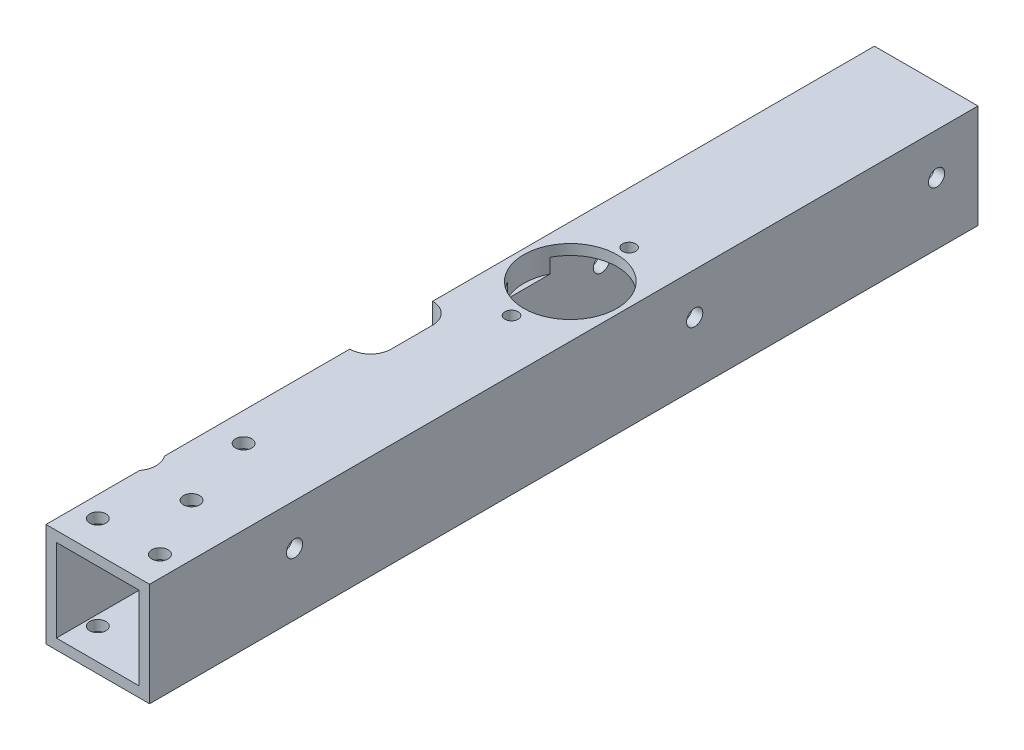
SolidWorks part; units mm, degrees
material "6061 Alloy"
ref_plane "Front Plane" through (0, 0, 0) normal (0, 0, 1) x (1, 0, 0)
ref_plane "Top Plane" through (0, 0, 0) normal (0, 1, 0) x (1, 0, 0)
ref_plane "Right Plane" through (0, 0, 0) normal (1, 0, 0) x (0, 0, -1)
sketch "Sketch1" plane through (0, 0, 0) normal (0, 0, 1) x (1, 0, 0)
  line L0 (-12.7, 12.7) -> (12.7, 12.7)
  line L2 (-15.875, 15.875) -> (15.875, 15.875)
  line L3 (-15.875, 15.875) -> (-15.875, -15.875)
  line L4 (-15.875, -15.875) -> (15.875, -15.875)
  line L5 (15.875, 15.875) -> (15.875, -15.875)
  line L10 (12.7, 12.7) -> (12.7, -12.7)
  line L11 (-12.7, -12.7) -> (12.7, -12.7)
  line L12 (-12.7, 12.7) -> (-12.7, -12.7)
  point P12 (0, 15.875)
  point P14 (15.875, 0)
  dimension "Wall Thickness" = 3.175
  dimension "Outside Width" = 31.75
  dimension "Outside Height" = 31.75
  dimension "Inside Height" = 25.4
  dimension "Inside Width" = 25.4
sketch "Sketch2" plane through (0, 0, 0) normal (1, 0, 0) x (0, 0, -1)
  line L0 (127, 0) -> (-127, 0)
  point P4 (0, 0)
  point P7 (-127, 0)
  point P10 (127, 0)
  dimension "Length" = 254
sketch "Sketch3" plane through (0, 0, 0) normal (0, 0, 1) x (1, 0, 0)
  line L21 (15.875, 15.875) -> (-15.875, 15.875)
  line L22 (15.875, -15.875) -> (15.875, 15.875)
  line L23 (-15.875, -15.875) -> (15.875, -15.875)
  line L24 (-15.875, 15.875) -> (-15.875, -15.875)
  line L25 (15.875, 15.875) -> (-15.875, 15.875)
  line L26 (15.875, -15.875) -> (15.875, 15.875)
  line L27 (-15.875, -15.875) -> (15.875, -15.875)
  line L28 (-15.875, 15.875) -> (-15.875, -15.875)
  line L29 (12.7, 12.7) -> (-12.7, 12.7)
  line L30 (12.7, -12.7) -> (12.7, 12.7)
  line L31 (-12.7, -12.7) -> (12.7, -12.7)
  line L32 (-12.7, 12.7) -> (-12.7, -12.7)
  line L33 (12.7, 12.7) -> (-12.7, 12.7)
  line L34 (12.7, -12.7) -> (12.7, 12.7)
  line L35 (-12.7, -12.7) -> (12.7, -12.7)
  line L36 (-12.7, 12.7) -> (-12.7, -12.7)
  dimension "D1" = 0
  dimension "D2" = 0
extrude "Boss-Extrude1" add sketch "Sketch3" along normal up to vertex (127 mm away) and the other way up to vertex (127 mm away) up to point (0, 0, 127) other way up to point (0, 0, -127)
sketch "Drawing Reference" plane through (0, 0, 0) normal (1, 0, 0) x (0, 0, -1)
  line L0 (-127, 0) -> (127, 0) construction
  line L1 (0, -15.875) -> (0, 15.875) construction
  line L2 (-127, -15.875) -> (127, -15.875) construction
  line L5 (-127, 15.875) -> (127, 15.875) construction
  point P7 (-104.14, 0)
  point P8 (104.14, 0)
  dimension "D1" = 22.86
sketch "Sketch4" plane through (0, 15.875, 0) normal (0, 1, 0) x (1, 0, 0)
  line L0 (0, -127) -> (0, -117.475) construction
  line L1 (15.875, -127) -> (-15.875, -127) construction
  line L2 (0, -117.475) -> (9.525, -117.475) construction
  line L3 (0, -117.475) -> (-9.525, -117.475) construction
  line L4 (0, -117.475) -> (0, 17.8816) construction
  line L5 (0, -117.475) -> (0, -98.2472) construction
  point P5 (-7.1119, -75.1713)
  dimension "D1" = 135.3566
  dimension "D2" = 19.05
  dimension "D3" = 9.525
hole_wizard "#10 Clearance Hole1" positions "Sketch5" profile "Sketch6" hole size "#10" standard "ANSI Inch" end condition through all
sketch "Sketch5" plane through (0, 15.875, 0) normal (0, 1, 0) x (1, 0, 0)
  point P0 (-9.525, -117.475)
  point P3 (9.525, -117.475)
  point P7 (0, -98.2472)
  point P10 (-7.1119, -75.1713)
sketch "Sketch6" plane through (-9.525, 15.875, 117.475) normal (1, 0, 0) x (0, 0, 1)
  line L0 (0, 0) -> (0, 31.75)
  line L1 (0, 31.75) -> (2.4892, 31.75)
  line L2 (2.4892, 31.75) -> (2.4892, 0)
  line L5 (2.4892, 0) -> (0, 0)
  line L11 (0, -6.35) -> (0, 107.95) construction
  dimension "Thru Hole Dia." = 4.9784
  dimension "Thru Hole Depth" = 31.75
sketch "Sketch7" plane through (0, 15.875, 0) normal (0, 1, 0) x (1, 0, 0)
  circle A0 centre (0, 17.8816) radius 14.2875
  dimension "D1" = 28.575
extrude "Cut-Extrude1" cut sketch "Sketch7" against normal blind 7.62
sketch "Sketch8" plane through (0, -15.875, 0) normal (0, -1, 0) x (1, 0, 0)
  circle A0 centre (0, -17.8816) radius 14.2875
  dimension "D1" = 28.575
extrude "Cut-Extrude2" cut sketch "Sketch8" against normal blind 7.62
sketch "Sketch9" plane through (0, -15.875, 0) normal (0, -1, 0) x (1, 0, 0)
  line L0 (-20.5727, 87.7258) -> (-42.1132, 74.2659) construction
  line L1 (-42.1132, 74.2659) -> (-15.875, 32.276) construction
  line L2 (-15.875, 127) -> (-15.875, -127) construction
  line L3 (-15.875, 32.276) -> (-9.099, 21.4322) construction
  line L4 (-15.875, 32.276) -> (-15.875, 27.5135) construction
  line L5 (-15.875, 27.5135) -> (-15.875, 14.8135) construction
  line L6 (-9.525, 27.5135) -> (-9.525, 14.8135)
  line L7 (-15.875, 8.4635) -> (-15.875, 33.8635)
  circle A0 centre (-15.875, 27.5135) radius 6.35 construction
  circle A1 centre (-15.875, 14.8135) radius 6.35 construction
  arc A2 (-15.875, 33.8635) -> (-9.525, 27.5135) centre (-15.875, 27.5135) cw
  arc A3 (-15.875, 8.4635) -> (-9.525, 14.8135) centre (-15.875, 14.8135) ccw
  dimension "D1" = 12.7
  dimension "D2" = 4.7625
extrude "Cut-Extrude3" cut sketch "Sketch9" against normal through all
sketch "Sketch10" plane through (15.875, 0, 0) normal (1, 0, 0) x (0, 0, -1)
  line L0 (-127, 3.175) -> (-82.55, 3.175) construction
  line L2 (-82.55, 3.175) -> (114.3, 3.175) construction
  line L3 (-127, -15.875) -> (-127, 3.175) construction
  line L4 (52.832, 3.175) -> (40.132, 3.175) construction
  line L5 (52.832, 434.0225) -> (52.832, -10.4775) construction
  dimension "D1" = 44.45
  dimension "D2" = 19.05
  dimension "D3" = 12.7
hole_wizard "#10 Clearance Hole2" positions "Sketch11" profile "Sketch12" hole size "#10" standard "ANSI Inch" end condition through all
sketch "Sketch11" plane through (15.875, 0, 0) normal (1, 0, 0) x (0, 0, -1)
  point P4 (-82.55, 3.175)
  point P7 (114.3, 3.175)
  point P12 (40.132, 3.175)
sketch "Sketch12" plane through (15.875, 3.175, 82.55) normal (0, 1, 0) x (0, 0, -1)
  line L0 (0, 0) -> (0, 31.75)
  line L1 (0, 31.75) -> (2.4892, 31.75)
  line L2 (2.4892, 31.75) -> (2.4892, 0)
  line L5 (2.4892, 0) -> (0, 0)
  line L11 (0, -6.35) -> (0, 107.95) construction
  dimension "Thru Hole Dia." = 4.9784
  dimension "Thru Hole Depth" = 31.75
sketch "Sketch13" plane through (0, -15.875, 0) normal (0, -1, 0) x (1, 0, 0)
  line L0 (-20.955, 94.5257) -> (-15.875, 94.5257) construction
  line L4 (-15.875, 127) -> (-15.875, 33.8635) construction
  circle A1 centre (-20.955, 94.5257) radius 6.35
  dimension "D1" = 5.08
extrude "Cut-Extrude4" cut sketch "Sketch13" against normal through all
sketch "Sketch14" plane through (0, -15.875, 0) normal (0, -1, 0) x (1, 0, 0)
  line L0 (0, -35.9156) -> (0, 0.1524) construction
  line L1 (0, 117.475) -> (0, -17.8816) construction
  line L2 (0, -17.8816) -> (5.4169, -17.8816) construction
  point P7 (0, -17.8816)
  dimension "D1" = 36.068
hole_wizard "Tap Drill for #10-32 Tap2" positions "Sketch17" profile "Sketch18" hole size "#10-32" standard "ANSI Inch"
sketch "Sketch17" plane through (0, 15.875, 0) normal (0, 1, 0) x (1, 0, 0)
  point P4 (0, 35.9156)
  point P9 (0, -0.1524)
sketch "Sketch18" plane through (0, 15.875, -35.9156) normal (1, 0, 0) x (0, 0, 1)
  line L0 (0, 0) -> (0, 6.2933)
  line L1 (0, 6.2933) -> (2.0193, 5.08)
  line L2 (2.0193, 5.08) -> (2.0193, 0)
  line L5 (2.0193, 0) -> (0, 0)
  line L10 (0, 6.2933) -> (-2.0193, 5.08) construction
  line L11 (0, -6.35) -> (0, 107.95) construction
  dimension "Hole Dia." = 4.0386
  dimension "Hole Depth" = 5.08
  dimension "Drill Angle" = 118
equation "\"D1@Drawing Reference\"=\"Outside Width@Sketch1\" * 0.72"
